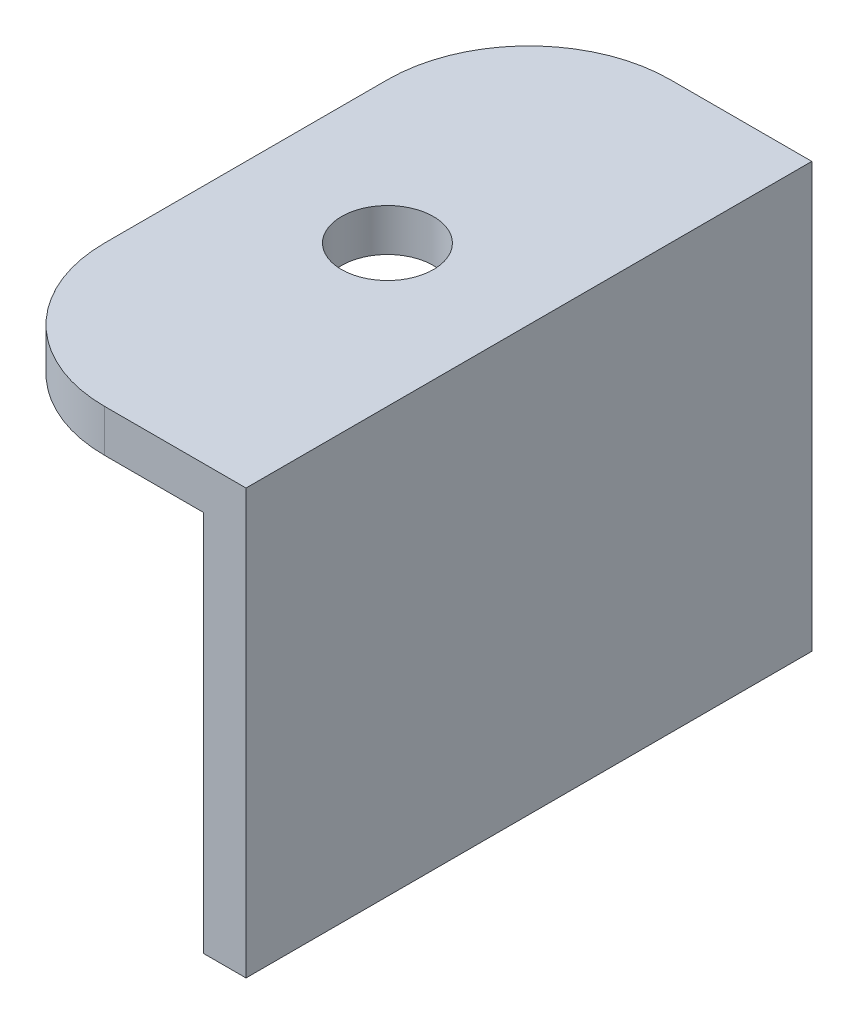
SolidWorks part; units mm, degrees
material "5052-H32"
ref_plane "正面" through (0, 0, 0) normal (0, 0, 1) x (1, 0, 0)
ref_plane "平面" through (0, 0, 0) normal (0, 1, 0) x (1, 0, 0)
ref_plane "右側面" through (0, 0, 0) normal (1, 0, 0) x (0, 0, -1)
sketch "ｽｹｯﾁ1" plane through (0, 0, 0) normal (0, 0, 1) x (1, 0, 0)
  line L0 (-20, 0) -> (0, 0)
  line L1 (0, 0) -> (0, -30)
  line L2 (0, -30) -> (-3, -30)
  line L3 (-3, -30) -> (-3, -3)
  line L4 (-3, -3) -> (-20, -3)
  line L5 (-20, -3) -> (-20, 0)
  dimension "D1" = 3
  dimension "D2" = 3
  dimension "D3" = 30
  dimension "D4" = 20
extrude "ﾎﾞｽ - 押し出し1" add sketch "ｽｹｯﾁ1" along normal blind 20 and the other way blind 20
sketch "ｽｹｯﾁ2" plane through (0, 0, 0) normal (0, 1, 0) x (1, 0, 0)
  circle A0 centre (-10, 0) radius 3.25
  dimension "D1" = 3.25
  dimension "D2" = 10
extrude "ｶｯﾄ - 押し出し1" cut sketch "ｽｹｯﾁ2" against normal blind 40
fillet "ﾌｨﾚｯﾄ1" radius 10 2 edges at (-20, -1.5, -20) (-20, -1.5, 20)
